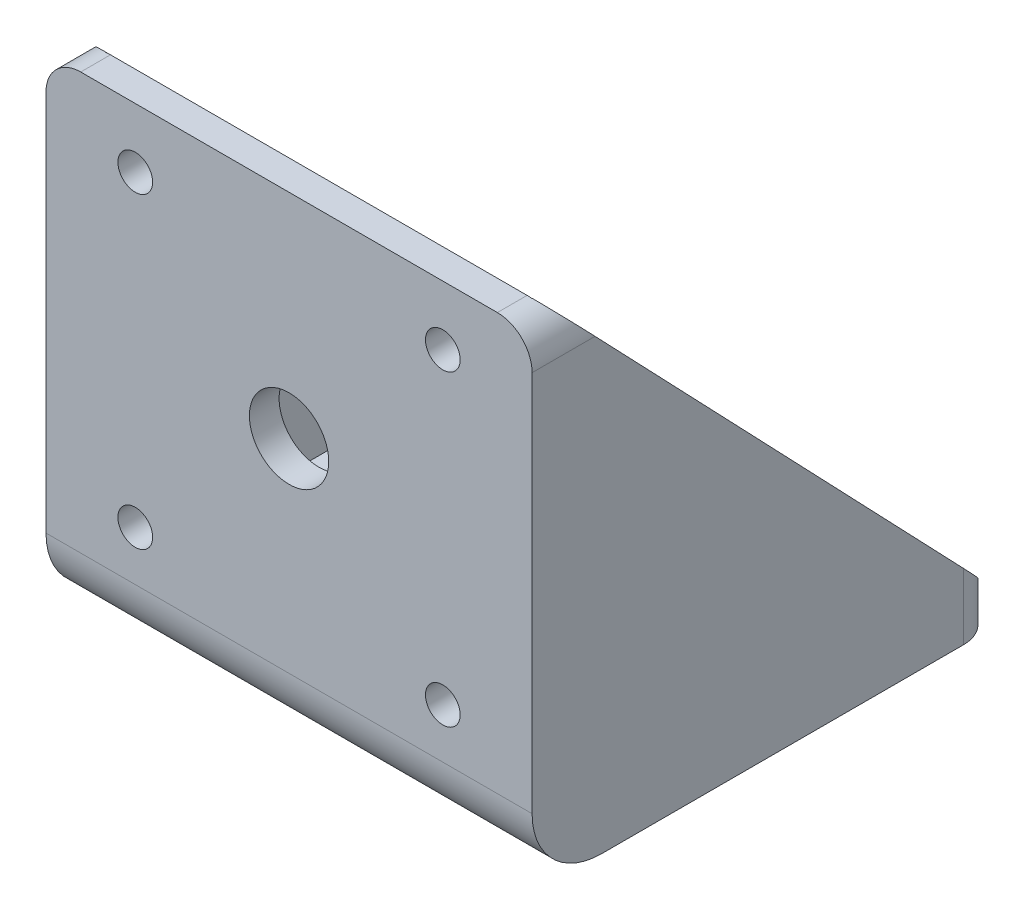
SolidWorks part; units mm, degrees
ref_plane "Plano frontal" through (0, 0, 0) normal (0, 0, 1) x (1, 0, 0)
ref_plane "Plano superior" through (0, 0, 0) normal (0, 1, 0) x (1, 0, 0)
ref_plane "Plano direito" through (0, 0, 0) normal (1, 0, 0) x (0, 0, -1)
sketch "Esboço1" plane through (0, 0, 0) normal (0, 1, 0) x (1, 0, 0)
  line L1 (-21.5, -23.5) -> (21.5, -23.5)
  line L2 (-21.5, -23.5) -> (-21.5, 23.5)
  line L3 (-21.5, 23.5) -> (21.5, 23.5)
  line L4 (21.5, -23.5) -> (21.5, 23.5)
  line L5 (-21.5, -23.5) -> (21.5, 23.5) construction
  line L6 (-21.5, 23.5) -> (21.5, -23.5) construction
  point P0 (0, 0)
  dimension "D1" = 43
  dimension "D2" = 47
extrude "Ressalto-extrusão1" add sketch "Esboço1" along normal blind 3
sketch "Esboço2" plane through (0, 3, 0) normal (0, 1, 0) x (1, 0, 0)
  line L0 (-21.5, -23.5) -> (-21.5, -20.5)
  line L1 (-21.5, 23.5) -> (-21.5, -23.5) construction
  line L2 (-21.5, -20.5) -> (21.5, -20.5)
  line L3 (21.5, -23.5) -> (21.5, 23.5) construction
  line L4 (21.5, -20.5) -> (21.5, -23.5)
  line L5 (21.5, -23.5) -> (-21.5, -23.5)
  dimension "D1" = 3
extrude "Ressalto-extrusão2" add sketch "Esboço2" along normal blind 46
sketch "Esboço3" plane through (0, 3, 0) normal (0, 1, 0) x (1, 0, 0)
  line L0 (0, 0) -> (14.945, 0) construction
  line L1 (0, 0) -> (0, 12.03) construction
  circle A0 centre (14.945, 12.03) radius 1.75
  circle A1 centre (14.945, -12.03) radius 1.75
  circle A2 centre (-14.945, -12.03) radius 1.75
  circle A3 centre (-14.945, 12.03) radius 1.75
  dimension "D3" = 3.5
  dimension "D1" = 12.03
  dimension "D2" = 14.945
  dimension "D4" = 14.945
  dimension "D5" = 12.03
extrude "Corte-extrusão1" cut sketch "Esboço3" against normal through all
sketch "Esboço4" plane through (0, 0, 23.5) normal (0, 0, 1) x (1, 0, 0)
  line L0 (-21.5, 49) -> (-21.5, 0) construction
  line L1 (-21.5, 49) -> (21.5, 49) construction
  line L4 (0, 0) -> (0, 49) construction
  line L5 (-21.5, 0) -> (21.5, 0) construction
  circle A0 centre (-15.5, 43) radius 1.75
  circle A1 centre (15.5, 43) radius 1.75
  circle A4 centre (-15.5, 12) radius 1.75
  circle A5 centre (15.5, 12) radius 1.75
  dimension "D3" = 3.5
  dimension "D1" = 6
  dimension "D2" = 6
  dimension "D4" = 12
  dimension "D5" = 6
extrude "Corte-extrusão2" cut sketch "Esboço4" against normal through all
sketch "Esboço5" plane through (-21.5, 0, 0) normal (-1, 0, 0) x (0, 0, 1)
  line L0 (-23.5, 0) -> (-23.5, 3)
  line L1 (-23.5, 3) -> (20.5, 49)
  line L2 (20.5, 49) -> (23.5, 49)
  line L3 (23.5, 49) -> (23.5, 0)
  line L4 (23.5, 0) -> (-23.5, 0)
extrude "Ressalto-extrusão3" add sketch "Esboço5" along normal blind 3
sketch "Esboço6" plane through (21.5, 0, 0) normal (1, 0, 0) x (0, 0, -1)
  line L0 (23.5, 0) -> (-23.5, 0)
  line L1 (-23.5, 0) -> (-23.5, 49)
  line L2 (-23.5, 49) -> (-20.5, 49)
  line L3 (-20.5, 49) -> (23.5, 3)
  line L4 (23.5, 3) -> (23.5, 0)
extrude "Ressalto-extrusão4" add sketch "Esboço6" along normal blind 3
sketch "Esboço7" plane through (0, 0, 23.5) normal (0, 0, 1) x (1, 0, 0)
  line L0 (-15.5, 43) -> (15.5, 12) construction
  circle A0 centre (0, 27.5) radius 4
  dimension "D1" = 8
extrude "Corte-extrusão3" cut sketch "Esboço7" against normal blind 3
fillet "Filete1" radius 3.5 2 edges at (-24.5, 49, 22) (24.5, 49, 22)
fillet "Filete2" radius 7 1 edges at (0, 0, 23.5)
fillet "Filete3" radius 3.5 2 edges at (-24.5, 1.5, -23.5) (24.5, 1.5, -23.5)
fillet "Filete4" radius 5 1 edges at (0, 3, 20.5)
